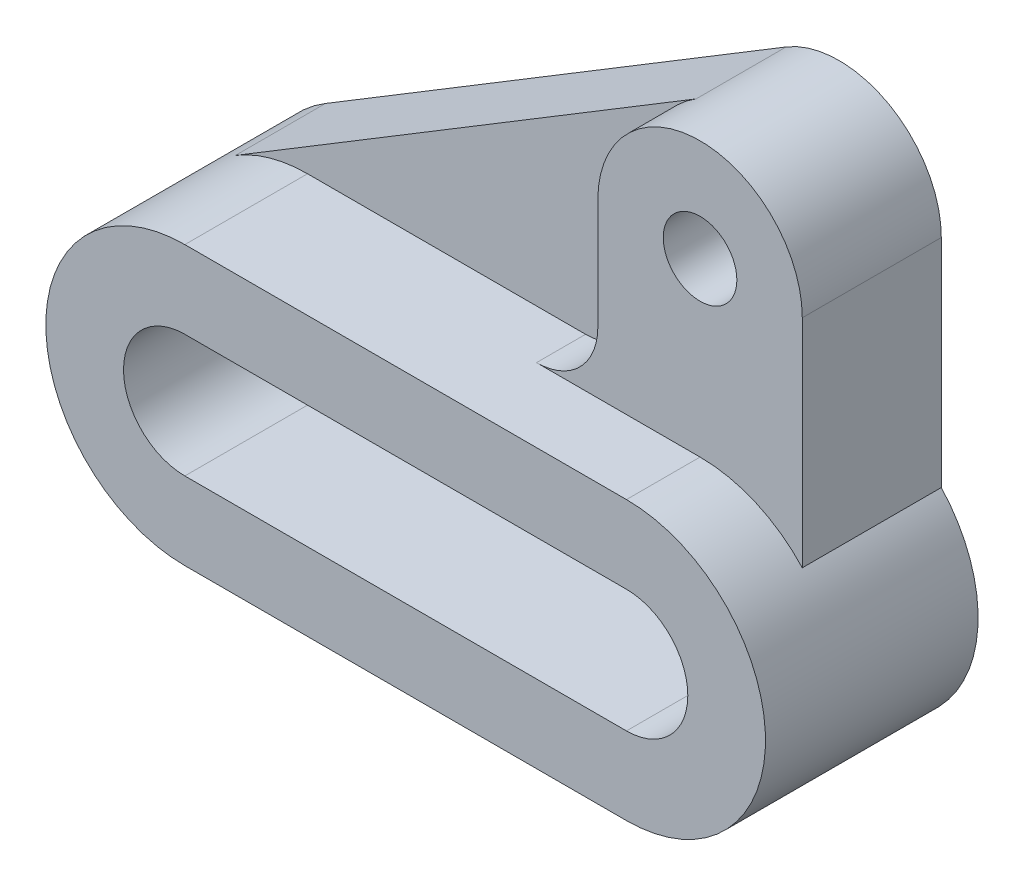
SolidWorks part; units mm, degrees
ref_plane "Front Plane" through (0, 0, 0) normal (0, 0, 1) x (1, 0, 0)
ref_plane "Top Plane" through (0, 0, 0) normal (0, 1, 0) x (1, 0, 0)
ref_plane "Right Plane" through (0, 0, 0) normal (1, 0, 0) x (0, 0, -1)
sketch "Sketch1" plane through (0, 0, 0) normal (0, 0, 1) x (1, 0, 0)
  line L0 (0, 0) -> (108, 0) construction
  line L1 (0, 15) -> (108, 15)
  line L2 (0, -15) -> (108, -15)
  line L3 (0, 34) -> (108, 34)
  line L4 (0, -34) -> (108, -34)
  line L5 (108, 0) -> (108, 76) construction
  line L6 (133, 76) -> (133, 23.0434)
  line L7 (83, 76) -> (83, 34)
  line L8 (-17.6263, 29.0743) -> (95.0395, 97.3781)
  arc A0 (0, 15) -> (0, -15) centre (0, 0) ccw
  arc A1 (108, -15) -> (108, 15) centre (108, 0) ccw
  arc A2 (108, -34) -> (108, 34) centre (108, 0) ccw
  arc A3 (0, 34) -> (0, -34) centre (0, 0) ccw
  circle A4 centre (108, 76) radius 9
  arc A5 (133, 76) -> (83, 76) centre (108, 76) ccw
  point P3 (54, 0)
  dimension "D1" = 15
  dimension "D4" = 18
  dimension "D5" = 50
  dimension "D2" = 108
  dimension "D6" = 76
  dimension "D3" = 19
extrude "Boss-Extrude1" add sketch "Sketch1" along normal blind 52 contours L3 A3 L4 A2 A1 L2 A0 L1 region at (41.5, 32.1132, 0)
extrude "Boss-Extrude2" add sketch "Sketch1<5>" along normal blind 22 contours A5 L8 A3 L3 L7 region at (52.3768, 53.0621, 0)
sketch "Sketch1<5>" plane through (0, 0, 0) normal (0, 0, 1) x (1, 0, 0) same geometry as "Sketch1"
extrude "Boss-Extrude3" add sketch "Sketch1<6>" along normal blind 34 contours L6 A5 L7 L3 A2 A4 region at (108.5503, 63.1215, 0)
sketch "Sketch1<6>" plane through (0, 0, 0) normal (0, 0, 1) x (1, 0, 0) same geometry as "Sketch1"
fillet "Fillet1" radius 15 1 edges at (83, 34, 28)
